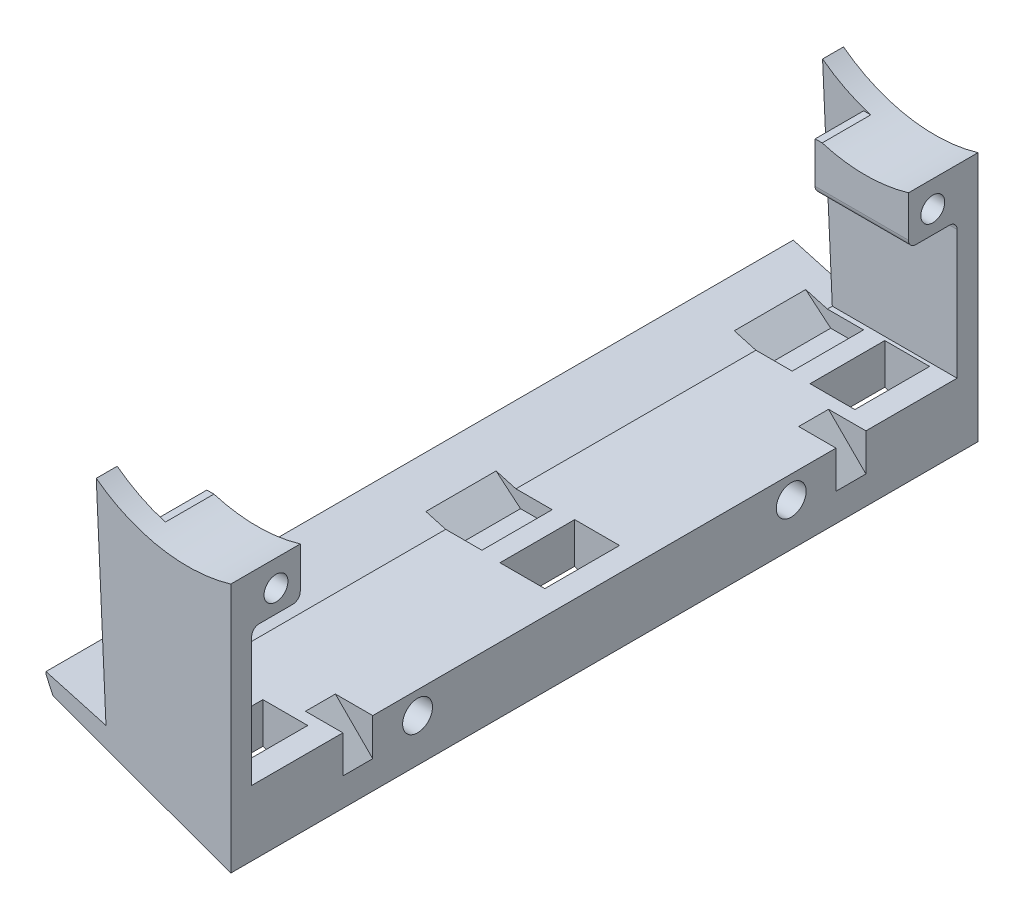
SolidWorks part; units mm, degrees
material "ABS"
ref_plane "Plano frontal" through (0, 0, 0) normal (0, 0, 1) x (1, 0, 0)
ref_plane "Plano superior" through (0, 0, 0) normal (0, 1, 0) x (1, 0, 0)
ref_plane "Plano direito" through (0, 0, 0) normal (1, 0, 0) x (0, 0, -1)
sketch "Esboço1" plane through (0, 0, 0) normal (0, 0, 1) x (1, 0, 0)
  line L0 (51, -6.7861) -> (51, -20.7861)
  line L1 (51, -20.7861) -> (26.2727, -11.7861)
  line L2 (26.2727, -11.7861) -> (26.2727, -6.7861)
  line L3 (26.2727, -6.7861) -> (51, -6.7861)
  dimension "D1" = 70
  dimension "D2" = 9
  dimension "D3" = 5
extrude "Ressalto-extrusão1" add sketch "Esboço1" against normal blind 100
sketch "Esboço2" plane through (0, 0, 0) normal (0, 0, 1) x (1, 0, 0)
  line L0 (34.3, -12.0261) -> (26.2727, -9.7861)
  line L1 (26.2727, -6.7861) -> (26.2727, -11.7861) construction
  line L4 (51, -20.7861) -> (51, -6.7861) construction
  line L5 (51, -12.0261) -> (51, -6.7861)
  line L6 (51, -6.7861) -> (26.2727, -6.7861)
  line L7 (51, -6.7861) -> (26.2727, -6.7861) construction
  line L8 (26.2727, -6.7861) -> (26.2727, -9.7861)
  line L9 (34.3, -12.0261) -> (49.5, -12.0261)
  line L11 (49.5, -12.0261) -> (51, -12.0261)
  dimension "D1" = 2
extrude "Corte-extrusão1" cut sketch "Esboço2" against normal blind 100
sketch "Esboço4" plane through (0, -12.0261, 0) normal (0, 1, 0) x (1, 0, 0)
  line L1 (41.8, 96.7261) -> (47.8, 96.7261)
  line L2 (41.8, 96.7261) -> (41.8, 86.7261)
  line L3 (41.8, 86.7261) -> (47.8, 86.7261)
  line L4 (47.8, 96.7261) -> (47.8, 86.7261)
  line L5 (41.8, 55.2261) -> (47.8, 55.2261)
  line L6 (41.8, 55.2261) -> (41.8, 45.2261)
  line L7 (41.8, 45.2261) -> (47.8, 45.2261)
  line L8 (47.8, 55.2261) -> (47.8, 45.2261)
  line L9 (41.8, 13.5) -> (47.8, 13.5)
  line L10 (41.8, 13.5) -> (41.8, 3.5)
  line L11 (41.8, 3.5) -> (47.8, 3.5)
  line L12 (47.8, 13.5) -> (47.8, 3.5)
extrude "Corte-extrusão3" cut sketch "Esboço4" against normal blind 100
sketch "Esboço6" plane through (0, -12.0261, 0) normal (0, 1, 0) x (1, 0, 0)
  line L1 (34.7496, 96.5375) -> (39.1437, 96.5375)
  line L2 (34.7496, 96.5375) -> (34.7496, 86.9838)
  line L3 (34.7496, 86.9838) -> (39.1437, 86.9838)
  line L4 (39.1437, 96.5375) -> (39.1437, 86.9838)
  line L5 (34.9108, 54.8658) -> (39.1437, 54.8658)
  line L6 (34.9108, 54.8658) -> (34.9108, 45.4647)
  line L7 (34.9108, 45.4647) -> (39.1437, 45.4647)
  line L8 (39.1437, 54.8658) -> (39.1437, 45.4647)
  line L9 (34.9108, 13.4978) -> (39.1437, 13.4978)
  line L10 (34.9108, 13.4978) -> (34.9108, 3.6931)
  line L11 (34.9108, 3.6931) -> (39.1437, 3.6931)
  line L12 (39.1437, 13.4978) -> (39.1437, 3.6931)
extrude "Corte-extrusão4" cut sketch "Esboço6" against normal blind 2
sketch "Esboço7" plane through (0, 0, -13.4978) normal (0, 0, 1) x (1, 0, 0)
  line L0 (34.9108, -12.0261) -> (34.9108, -14.0261)
  line L1 (39.1437, -12.0261) -> (34.9108, -12.0261) construction
  line L2 (34.9108, -14.0261) -> (34.9108, -12.0261) construction
  line L3 (39.1437, -14.0261) -> (34.9108, -14.0261) construction
  line L4 (34.9108, -14.0261) -> (31.644, -11.285)
  line L5 (26.2727, -9.7861) -> (34.3, -12.0261) construction
  line L6 (31.644, -11.285) -> (34.9108, -12.0261)
  dimension "D1" = 50
extrude "Corte-extrusão5" cut sketch "Esboço7" along normal up to surface (9.8048 mm away) up to face at (37.0273, -13.0261, -3.6931)
sketch "Esboço8" plane through (0, 0, -54.8658) normal (0, 0, 1) x (1, 0, 0)
  line L0 (34.9108, -14.0261) -> (34.9108, -12.0261)
  line L1 (34.9108, -14.0261) -> (34.9108, -12.0261) construction
  line L2 (34.9108, -12.0261) -> (31.3355, -11.0261)
  line L3 (31.3355, -11.0261) -> (34.9108, -14.0261)
  dimension "D1" = 50
  dimension "D2" = 3
extrude "Corte-extrusão6" cut sketch "Esboço8" along normal up to surface (9.4012 mm away) up to face at (37.0273, -13.0261, -45.4647)
sketch "Esboço9" plane through (0, 0, -96.5375) normal (0, 0, 1) x (1, 0, 0)
  line L0 (34.7496, -14.0261) -> (34.7496, -12.0261)
  line L1 (34.7496, -14.0261) -> (34.7496, -12.0261) construction
  line L2 (34.7496, -12.0261) -> (30.1656, -10.1797)
  line L3 (30.1656, -10.1797) -> (34.7496, -14.0261)
  dimension "D1" = 50
extrude "Corte-extrusão7" cut sketch "Esboço9" along normal up to surface (9.5537 mm away) up to face at (36.9466, -13.0261, -86.9838)
sketch "Esboço10" plane through (0, 0, 0) normal (0, 0, 1) x (1, 0, 0)
  line L0 (51, -12.0261) -> (51, 9.9739)
  line L1 (34.3, -12.0261) -> (51, -12.0261) construction
  line L2 (51, -20.7861) -> (51, -12.0261) construction
  line L3 (45.8019, 12.7473) -> (33, 15.9739)
  line L4 (33, 15.9739) -> (34.3, -12.0261)
  line L5 (26.2727, -9.7861) -> (34.3, -12.0261) construction
  line L6 (51, 9.9739) -> (51, 12.7139)
  line L7 (49.5411, 12.7473) -> (45.8019, 12.7473)
  line L8 (51, 12.7139) -> (49.5411, 12.7473)
  line L9 (34.3, -12.0261) -> (51, -12.0261)
  dimension "D1" = 18
  dimension "D2" = 22
  dimension "D3" = 28
extrude "Ressalto-extrusão2" add sketch "Esboço10" against normal blind 2.8
sketch "Esboço11" plane through (0, 0, -100) normal (0, 0, -1) x (-1, 0, 0)
  line L0 (-34.3, -12.0261) -> (-33, 15.9739)
  line L1 (-26.2727, -9.7861) -> (-34.3, -12.0261) construction
  line L2 (-33, 15.9739) -> (-34.3, -12.0261) construction
  line L3 (-33, 15.9739) -> (-45.2716, 12.7473)
  line L4 (-49.5411, 12.7473) -> (-45.8019, 12.7473) construction
  line L5 (-45.2716, 12.7473) -> (-49.5411, 12.7473)
  line L6 (-51, 12.7139) -> (-49.5411, 12.7473) construction
  line L7 (-49.5411, 12.7473) -> (-51, 12.7139)
  line L8 (-51, 12.7139) -> (-51, -12.0261)
  line L9 (-34.3, -12.0261) -> (-51, -12.0261) construction
  line L10 (-51, -12.0261) -> (-34.3, -12.0261)
extrude "Ressalto-extrusão3" add sketch "Esboço11" against normal blind 2.8
chamfer "Chanfro1" distance 1 angle 45 1 edges at (26.2727, -11.7861, -50) first distance on face at (44.8, -18.5295, -91.7261)
sketch "Esboço12" plane through (51, 0, 0) normal (1, 0, 0) x (0, 0, -1)
  line L0 (97.2, -12.0261) -> (2.8, -12.0261) construction
  line L1 (100, -20.7861) -> (100, 12.7139) construction
  circle A0 centre (75, -15.0261) radius 2
  circle A1 centre (25, -15.0261) radius 2
  dimension "D1" = 4
  dimension "D2" = 3
  dimension "D3" = 4
  dimension "D4" = 3
  dimension "D5" = 50
  dimension "D6" = 25
extrude "Corte-extrusão8" cut sketch "Esboço12" against normal blind 5
sketch "Esboço14" plane through (51, 0, 0) normal (1, 0, 0) x (0, 0, -1)
  line L0 (2.8, 15.9739) -> (2.8, -12.0261) construction
  line L1 (2.8, 12.7139) -> (9.3, 12.7139)
  line L2 (2.8, 12.7139) -> (2.8, 6.2139)
  line L3 (2.8, 6.2139) -> (9.3, 6.2139)
  line L4 (9.3, 12.7139) -> (9.3, 6.2139)
  line L5 (97.2, -12.0261) -> (97.2, 15.9739) construction
  line L6 (97.2, 12.7139) -> (90.7, 12.7139)
  line L7 (97.2, 12.7139) -> (97.2, 6.2139)
  line L8 (97.2, 6.2139) -> (90.7, 6.2139)
  line L9 (90.7, 12.7139) -> (90.7, 6.2139)
  line L10 (97.2, 12.7139) -> (100, 12.7139) construction
  line L11 (2.8, 12.7139) -> (0, 12.7139) construction
  dimension "D1" = 6.5
  dimension "D2" = 6.5
  dimension "D3" = 6.5
  dimension "D4" = 6.5
  dimension "D5" = 0
  dimension "D6" = 0
extrude "Ressalto-extrusão4" add sketch "Esboço14" against normal blind 12.5
sketch "Esboço15" plane through (0, 0, 0) normal (0, 0, 1) x (1, 0, 0)
  line L10 (45.8019, 12.7473) -> (33, 15.9739) construction
  line L11 (51, -20.7861) -> (51, 12.7139) construction
  line L12 (51, 12.7139) -> (49.5411, 12.7473) construction
  arc A0 (33, 15.9739) -> (51, 12.7139) centre (45.2218, 32.1335) ccw
  arc A1 (33, 15.9739) -> (51, 12.7139) centre (37.5555, -10.1968) cw
extrude "Corte-extrusão9" cut sketch "Esboço15" against normal blind 100
sketch "Esboço17" plane through (38.5, 0, 0) normal (-1, 0, 0) x (0, 0, 1)
  line L0 (-2.8, 15.9739) -> (-2.8, -12.0261) construction
  line L1 (-2.8, 6.2139) -> (-9.3, 6.2139) construction
  line L2 (-97.2, -12.0261) -> (-97.2, 15.9739) construction
  circle A0 centre (-6.05, 9.2139) radius 1.6
  circle A1 centre (-93.95, 9.2139) radius 1.6
  dimension "D1" = 3.25
  dimension "D3" = 3.25
  dimension "D2" = 3
extrude "Corte-extrusão10" cut sketch "Esboço17" against normal blind 100
fillet "Filete1" radius 1 4 edges at (44.75, 6.2139, -90.7) (44.75, 6.2139, -97.2) (44.75, 6.2139, -2.8) (44.75, 6.2139, -9.3)
sketch "Esboço18" plane through (0, -12.0261, 0) normal (0, 1, 0) x (1, 0, 0)
  line L0 (51, 97.2) -> (51, 2.8) construction
  line L1 (51, 15) -> (46, 15)
  line L2 (51, 15) -> (51, 19)
  line L3 (51, 19) -> (46, 19)
  line L4 (46, 15) -> (46, 19)
  line L5 (33, 0) -> (51, 0) construction
  line L6 (23.5985, 50) -> (64.3506, 50) construction
  line L7 (51, 85) -> (51, 81)
  line L8 (51, 85) -> (46, 85)
  line L9 (46, 85) -> (46, 81)
  line L10 (51, 81) -> (46, 81)
  dimension "D1" = 4
  dimension "D2" = 5
  dimension "D3" = 15
extrude "Corte-extrusão11" cut sketch "Esboço18" against normal blind 5
chamfer "Chanfro2" distance 5 angle 45 2 edges at (46, -17.0261, -83) (46, -17.0261, -17)
